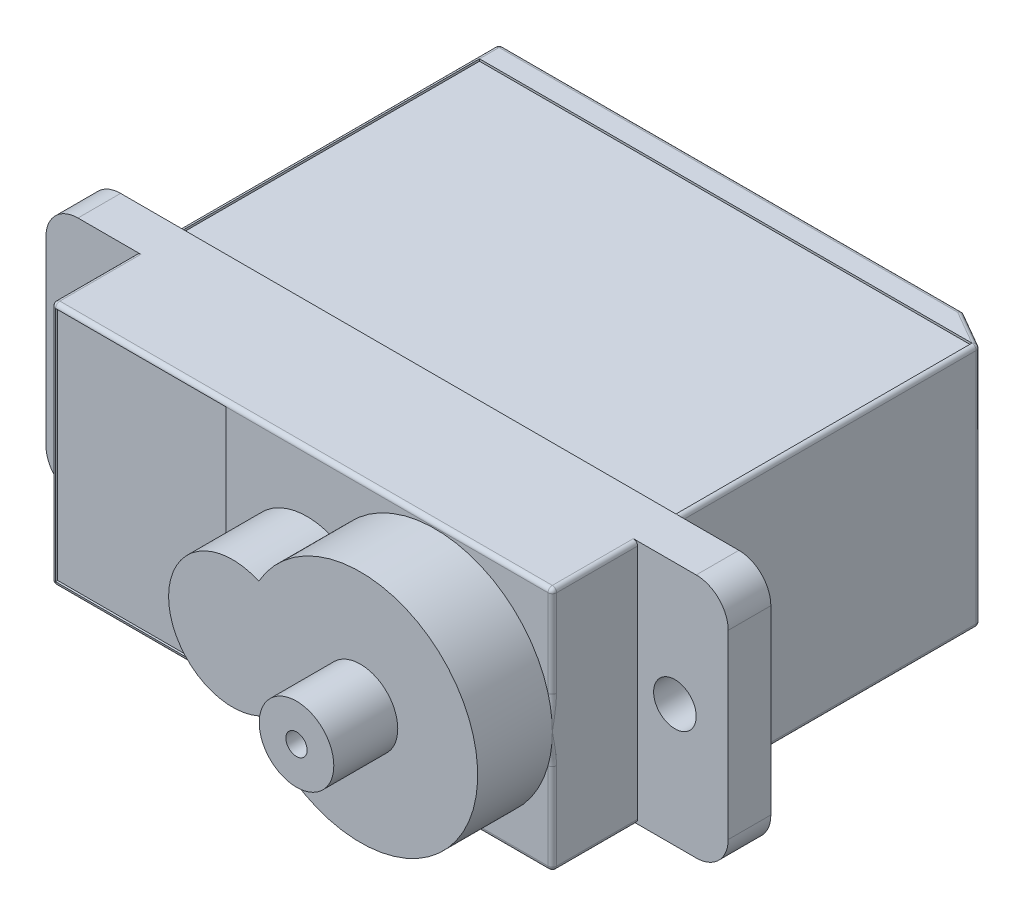
SolidWorks part; units mm, degrees
ref_plane "Plano frontal" through (0, 0, 0) normal (0, 0, 1) x (1, 0, 0)
ref_plane "Plano superior" through (0, 0, 0) normal (0, 1, 0) x (1, 0, 0)
ref_plane "Plano direito" through (0, 0, 0) normal (1, 0, 0) x (0, 0, -1)
sketch "Esboço4" plane through (0, 0, 0) normal (0, 1, 0) x (1, 0, 0)
  line L0 (0, 10.5) -> (0, -10.5) construction
  line L1 (-11.75, -10.5) -> (11.75, -10.5)
  line L28 (11.75, 10.5) -> (-11.75, 10.5)
  line L29 (-11.75, 10.5) -> (-11.75, -4.5)
  line L30 (-11.75, -4.5) -> (-16, -4.5)
  line L31 (-16, -4.5) -> (-16, -6.5)
  line L32 (-16, -6.5) -> (-11.75, -6.5)
  line L33 (-11.75, -6.5) -> (-11.75, -10.5)
  line L37 (11.75, -10.5) -> (11.75, -6.5)
  line L38 (11.75, -6.5) -> (16, -6.5)
  line L39 (16, -6.5) -> (16, -4.5)
  line L40 (16, -4.5) -> (11.75, -4.5)
  line L41 (11.75, -4.5) -> (11.75, 10.5)
  dimension "D1" = 23.5
  dimension "D2" = 15
  dimension "D3" = 32
  dimension "D6" = 4
  dimension "D7" = 2
extrude "Ressalto-extrusão4" add sketch "Esboço4" along normal mid plane 11.5
sketch "Esboço8" plane through (0, 0, 10.5) normal (0, 0, 1) x (1, 0, 0)
  line L3 (11.75, 5.75) -> (11.75, -5.75) construction
  circle A0 centre (6.25, 0) radius 5.5
  dimension "D1" = 11
extrude "Ressalto-extrusão7" add sketch "Esboço8" along normal blind 3.5
sketch "Esboço9" plane through (0, 0, 14) normal (0, 0, 1) x (1, 0, 0)
  circle A0 centre (6.25, 0) radius 1.75
  circle A1 centre (6.25, 0) radius 0.5
  dimension "D1" = 3.5
  dimension "D2" = 1
extrude "Ressalto-extrusão8" add sketch "Esboço9" along normal blind 3
sketch "Esboço10" plane through (0, 0, 10.5) normal (0, 0, 1) x (1, 0, 0)
  circle A0 centre (0.25, 0) radius 3
  circle A2 centre (6.25, 0) radius 0.5 construction
  dimension "D1" = 6
  dimension "D2" = 6
extrude "Ressalto-extrusão9" add sketch "Esboço10" along normal up to surface (3.5 mm away) up to face at (11.75, 0, 14)
chamfer "Chanfro1" distance 1 angle 60 1 edges at (11.75, 0, -10.5) first distance on face at (11.75, 0, -3)
sketch "Esboço12" plane through (0, 0, 6.5) normal (0, 0, 1) x (1, 0, 0)
  line L0 (-13.5, 0) -> (13.5, 0) construction
  circle A0 centre (-13.5, 0) radius 1
  circle A1 centre (13.5, 0) radius 1
  dimension "D2" = 2
  dimension "D1" = 27
extrude "Corte-extrusão1" cut sketch "Esboço12" against normal through all
fillet "Filete1" radius 1.5 4 edges at (-16, 5.75, 5.5) (-16, -5.75, 5.5) (16, 5.75, 5.5) (16, -5.75, 5.5)
fillet "Filete2" radius 0.2 19 edges at (11.75, -2.875, 10.5) (11.75, 2.875, 10.5) (11.75, 0, -9.5) (-0.866, 5.75, -10.5) (10.884, 5.75, -10) (11.75, 5.75, 8.5) (11.75, 5.75, -2.5) (0, 5.75, 10.5) (-11.75, 5.75, 8.5) (-0.866, -5.75, -10.5) (10.884, -5.75, -10) (11.75, -5.75, -2.5) (11.75, -5.75, 8.5) (0, -5.75, 10.5) (-11.75, 0, 10.5) (-11.75, -5.75, 8.5) (-11.75, 0, -10.5) (-11.75, 5.75, -3) (-11.75, -5.75, -3)
sketch "Esboço13" plane through (0, -5.75, 0) normal (0, -1, 0) x (1, 0, 0)
  line L1 (-11.55, 4.5) -> (11.55, 4.5)
  line L2 (-11.55, 4.5) -> (-11.55, -9.3845)
  line L3 (-11.55, -9.3845) -> (11.55, -9.3845)
  line L4 (11.55, 4.5) -> (11.55, -9.3845)
extrude "Corte-extrusão2" cut sketch "Esboço13" against normal blind 0.1
sketch "Esboço14" plane through (0, 0, 10.5) normal (0, 0, 1) x (1, 0, 0)
  line L0 (-11.55, -5.55) -> (11.55, -5.55) construction
  line L1 (-11.55, 5.55) -> (-3.55, 5.55)
  line L2 (-11.55, 5.55) -> (-11.55, -5.55)
  line L3 (-11.55, -5.55) -> (-3.55, -5.55)
  line L4 (-3.55, 5.55) -> (-3.55, -5.55)
  dimension "D1" = 8
extrude "Corte-extrusão3" cut sketch "Esboço14" against normal blind 0.1
sketch "Esboço15" plane through (0, 0, 0) normal (0, 0, 1) x (1, 0, 0)
  line L0 (-16, 4.25) -> (-16, -4.25) construction
  line L1 (-16, 0) -> (16, 0)
  line L2 (-16, 0) -> (-16, 5.75)
  line L3 (-16, 5.75) -> (16, 5.75)
  line L4 (16, 0) -> (16, 5.75)
  line L5 (-11.55, 5.75) -> (11.55, 5.75) construction
  line L6 (16, 4.25) -> (16, -4.25) construction
extrude "Corte-extrusão4" cut sketch "Esboço15" against normal through all and the other way through all
mirror "Espelhar1" about plane through (-16, 0, -10.5) normal (0, -1, 0) of bodies 116
